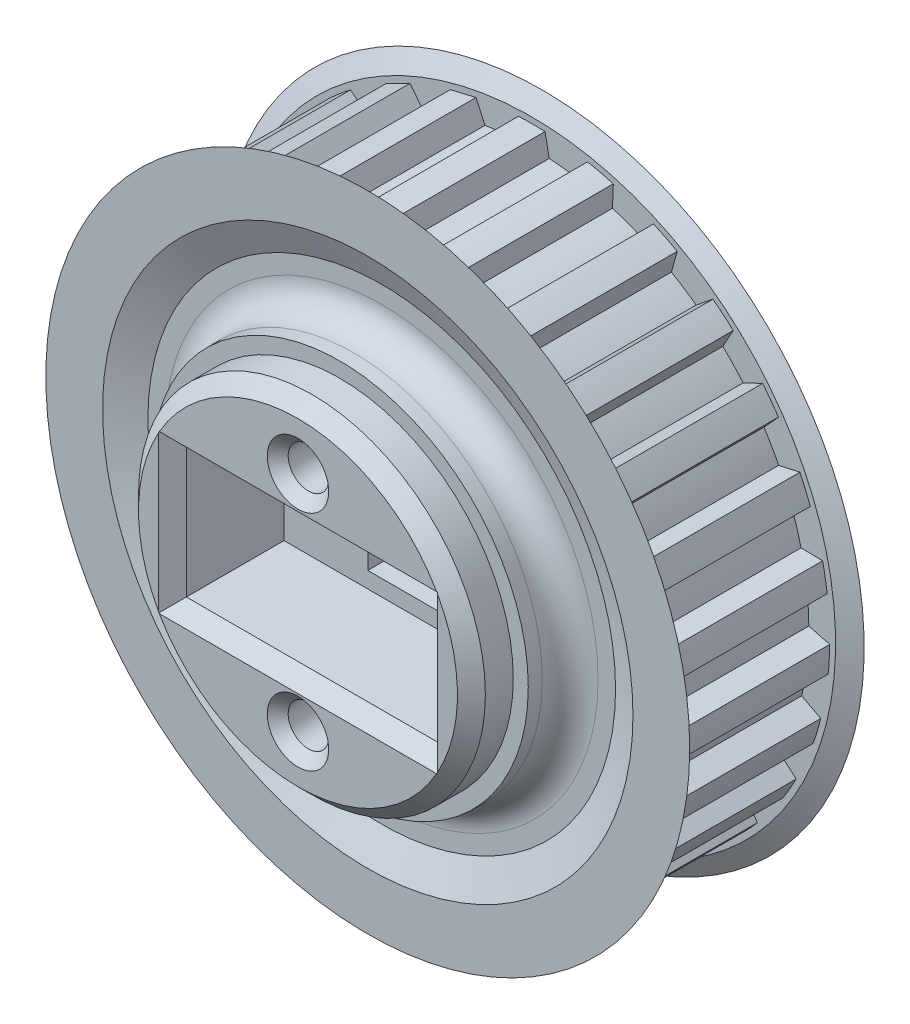
SolidWorks part; units mm, degrees
other "Markup1"
sketch "Sketch8" plane through (-22.8072, 22.8072, -5) normal (-0.0228, 0.8013, -0.5978) x (-0.0343, -0.5983, -0.8006)
sketch "Sketch9" plane through (-23.067, 23.067, -5.7421) normal (-0.0228, 0.8013, -0.5978) x (-0.0343, -0.5983, -0.8006)
sketch "Sketch10" plane through (-23.067, 23.067, -5.7421) normal (-0.0228, 0.8013, -0.5978) x (-0.0343, -0.5983, -0.8006)
material "ABS"
ref_plane "Alzado" through (0, 0, 0) normal (0, 0, 1) x (1, 0, 0)
ref_plane "Planta" through (0, 0, 0) normal (0, 1, 0) x (1, 0, 0)
ref_plane "Vista lateral" through (0, 0, 0) normal (1, 0, 0) x (0, 0, -1)
sketch "Croquis1" plane through (0, 0, 0) normal (0, 0, 1) x (1, 0, 0)
  line L0 (0, 0) -> (0, 14.5885) construction
  line L1 (-0.95, 21.3289) -> (-1.25, 19.8106)
  line L2 (0.95, 21.3289) -> (1.25, 19.8106)
  line L3 (5.8432, 20.5348) -> (5.7849, 18.9883)
  line L4 (3.9944, 20.973) -> (3.3523, 19.5649)
  line L5 (10.4213, 18.6338) -> (10.008, 17.1424)
  line L6 (8.7234, 19.4865) -> (7.7739, 18.2644)
  line L7 (14.4377, 15.7282) -> (13.6916, 14.3723)
  line L8 (12.9822, 16.9495) -> (11.7765, 15.9793)
  line L9 (17.6757, 11.9747) -> (16.637, 10.8274)
  line L10 (16.5411, 13.4987) -> (15.1441, 12.8327)
  line L11 (19.9608, 7.5756) -> (18.6855, 6.6988)
  line L12 (19.2082, 9.3202) -> (17.6953, 8.9943)
  line L13 (21.1698, 2.7681) -> (19.7267, 2.2091)
  line L14 (20.8399, 4.6393) -> (19.2926, 4.6711)
  line L15 (21.2375, -2.1886) -> (19.7044, -2.3998)
  line L16 (21.348, -0.2918) -> (19.8498, 0.096)
  line L17 (20.1604, -7.0273) -> (18.6198, -6.8792)
  line L18 (20.7053, -5.2071) -> (19.3369, -4.4843)
  line L19 (17.9963, -11.4872) -> (16.5315, -10.9878)
  line L20 (18.9463, -9.8417) -> (17.7815, -8.8228)
  line L21 (14.8621, -15.3278) -> (13.5519, -14.5041)
  line L22 (16.166, -13.9457) -> (15.2675, -12.6856)
  line L23 (10.9267, -18.342) -> (9.8417, -17.2384)
  line L24 (12.5141, -17.298) -> (11.9305, -15.8646)
  line L25 (6.4022, -20.3675) -> (5.601, -19.0434)
  line L26 (8.1876, -19.7176) -> (7.9502, -18.1884)
  line L27 (1.5326, -21.2949) -> (1.0583, -19.8218)
  line L28 (3.4197, -21.0743) -> (3.5414, -19.5315)
  line L29 (-3.4197, -21.0743) -> (-3.5414, -19.5315)
  line L30 (-1.5326, -21.2949) -> (-1.0583, -19.8218)
  line L31 (-8.1876, -19.7176) -> (-7.9502, -18.1884)
  line L32 (-6.4022, -20.3675) -> (-5.601, -19.0434)
  line L33 (-12.5141, -17.298) -> (-11.9305, -15.8646)
  line L34 (-10.9267, -18.342) -> (-9.8417, -17.2384)
  line L35 (-16.166, -13.9457) -> (-15.2675, -12.6856)
  line L36 (-14.8621, -15.3278) -> (-13.5519, -14.5041)
  line L37 (-18.9463, -9.8417) -> (-17.7815, -8.8228)
  line L38 (-17.9963, -11.4872) -> (-16.5315, -10.9878)
  line L39 (-20.7053, -5.2071) -> (-19.3369, -4.4843)
  line L40 (-20.1604, -7.0273) -> (-18.6198, -6.8792)
  line L41 (-21.348, -0.2918) -> (-19.8498, 0.096)
  line L42 (-21.2375, -2.1886) -> (-19.7044, -2.3998)
  line L43 (-20.8399, 4.6393) -> (-19.2926, 4.6711)
  line L44 (-21.1698, 2.7681) -> (-19.7267, 2.2091)
  line L45 (-19.2082, 9.3202) -> (-17.6953, 8.9943)
  line L46 (-19.9608, 7.5756) -> (-18.6855, 6.6988)
  line L47 (-16.5411, 13.4987) -> (-15.1441, 12.8327)
  line L48 (-17.6757, 11.9747) -> (-16.637, 10.8274)
  line L49 (-12.9822, 16.9495) -> (-11.7765, 15.9793)
  line L50 (-14.4377, 15.7282) -> (-13.6916, 14.3723)
  line L51 (-8.7234, 19.4865) -> (-7.7739, 18.2644)
  line L52 (-10.4213, 18.6338) -> (-10.008, 17.1424)
  line L53 (-10.4213, 18.6338) -> (-8.7234, 19.4865)
  line L54 (-3.9944, 20.973) -> (-3.3523, 19.5649)
  line L55 (-5.8432, 20.5348) -> (-5.7849, 18.9883)
  line L56 (-5.8432, 20.5348) -> (-3.9944, 20.973)
  arc A0 (-10.008, 17.1424) -> (-11.7765, 15.9793) centre (0, 0) ccw
  arc A1 (3.3523, 19.5649) -> (1.25, 19.8106) centre (0, 0) ccw
  arc A2 (-5.7849, 18.9883) -> (-7.7739, 18.2644) centre (0, 0) ccw
  arc A9 (-12.9822, 16.9495) -> (-14.4377, 15.7282) centre (0, 0) ccw
  arc A10 (-16.5411, 13.4987) -> (-17.6757, 11.9747) centre (0, 0) ccw
  arc A11 (5.8432, 20.5348) -> (3.9944, 20.973) centre (0, 0) ccw
  arc A12 (0.95, 21.3289) -> (-0.95, 21.3289) centre (0, 0) ccw
  arc A16 (10.4213, 18.6338) -> (8.7234, 19.4865) centre (0, 0) ccw
  arc A17 (14.4377, 15.7282) -> (12.9822, 16.9495) centre (0, 0) ccw
  arc A18 (17.6757, 11.9747) -> (16.5411, 13.4987) centre (0, 0) ccw
  arc A19 (19.9608, 7.5756) -> (19.2082, 9.3202) centre (0, 0) ccw
  arc A20 (21.1698, 2.7681) -> (20.8399, 4.6393) centre (0, 0) ccw
  arc A21 (21.2375, -2.1886) -> (21.348, -0.2918) centre (0, 0) ccw
  arc A22 (20.1604, -7.0273) -> (20.7053, -5.2071) centre (0, 0) ccw
  arc A23 (17.9963, -11.4872) -> (18.9463, -9.8417) centre (0, 0) ccw
  arc A24 (14.8621, -15.3278) -> (16.166, -13.9457) centre (0, 0) ccw
  arc A25 (10.9267, -18.342) -> (12.5141, -17.298) centre (0, 0) ccw
  arc A26 (-8.1876, -19.7176) -> (-6.4022, -20.3675) centre (0, 0) ccw
  arc A27 (-12.5141, -17.298) -> (-10.9267, -18.342) centre (0, 0) ccw
  arc A28 (-16.166, -13.9457) -> (-14.8621, -15.3278) centre (0, 0) ccw
  arc A29 (-20.7053, -5.2071) -> (-20.1604, -7.0273) centre (0, 0) ccw
  arc A30 (-21.348, -0.2918) -> (-21.2375, -2.1886) centre (0, 0) ccw
  arc A31 (-20.8399, 4.6393) -> (-21.1698, 2.7681) centre (0, 0) ccw
  arc A32 (-19.2082, 9.3202) -> (-19.9608, 7.5756) centre (0, 0) ccw
  arc A33 (-3.4197, -21.0743) -> (-1.5326, -21.2949) centre (0, 0) ccw
  arc A34 (1.5326, -21.2949) -> (3.4197, -21.0743) centre (0, 0) ccw
  arc A35 (6.4022, -20.3675) -> (8.1876, -19.7176) centre (0, 0) ccw
  arc A36 (7.7739, 18.2644) -> (5.7849, 18.9883) centre (0, 0) ccw
  arc A37 (11.7765, 15.9793) -> (10.008, 17.1424) centre (0, 0) ccw
  arc A39 (-1.25, 19.8106) -> (-3.3523, 19.5649) centre (0, 0) ccw
  arc A43 (15.1441, 12.8327) -> (13.6916, 14.3723) centre (0, 0) ccw
  arc A44 (17.6953, 8.9943) -> (16.637, 10.8274) centre (0, 0) ccw
  arc A45 (19.2926, 4.6711) -> (18.6855, 6.6988) centre (0, 0) ccw
  arc A46 (19.8498, 0.096) -> (19.7267, 2.2091) centre (0, 0) ccw
  arc A47 (19.3369, -4.4843) -> (19.7044, -2.3998) centre (0, 0) ccw
  arc A48 (17.7815, -8.8228) -> (18.6198, -6.8792) centre (0, 0) ccw
  arc A49 (15.2675, -12.6856) -> (16.5315, -10.9878) centre (0, 0) ccw
  arc A50 (11.9305, -15.8646) -> (13.5519, -14.5041) centre (0, 0) ccw
  arc A51 (7.9502, -18.1884) -> (9.8417, -17.2384) centre (0, 0) ccw
  arc A52 (3.5414, -19.5315) -> (5.601, -19.0434) centre (0, 0) ccw
  arc A53 (-1.0583, -19.8218) -> (1.0583, -19.8218) centre (0, 0) ccw
  arc A54 (-5.601, -19.0434) -> (-3.5414, -19.5315) centre (0, 0) ccw
  arc A55 (-9.8417, -17.2384) -> (-7.9502, -18.1884) centre (0, 0) ccw
  arc A56 (-13.5519, -14.5041) -> (-11.9305, -15.8646) centre (0, 0) ccw
  arc A57 (-16.5315, -10.9878) -> (-15.2675, -12.6856) centre (0, 0) ccw
  arc A58 (-18.6198, -6.8792) -> (-17.7815, -8.8228) centre (0, 0) ccw
  arc A59 (-19.7044, -2.3998) -> (-19.3369, -4.4843) centre (0, 0) ccw
  arc A60 (-19.7267, 2.2091) -> (-19.8498, 0.096) centre (0, 0) ccw
  arc A61 (-18.6855, 6.6988) -> (-19.2926, 4.6711) centre (0, 0) ccw
  arc A62 (-16.637, 10.8274) -> (-17.6953, 8.9943) centre (0, 0) ccw
  arc A63 (-13.6916, 14.3723) -> (-15.1441, 12.8327) centre (0, 0) ccw
  arc A71 (-18.9463, -9.8417) -> (-17.9963, -11.4872) centre (0, 0) ccw
  circle A72 centre (0, 0) radius 1.5
  point P151 (0, 0)
  dimension "D1" = 21.35
  dimension "D6" = 3
  dimension "D5" = 1.5
  dimension "D2" = 2.5
  dimension "D3" = 1.9
  dimension "D4" = 27
extrude "Saliente-Extruir1" add sketch "Croquis1" along normal blind 11
sketch "Croquis2" plane through (0, 0, 11) normal (0, 0, 1) x (1, 0, 0)
  circle A0 centre (0, 0) radius 23.5
  circle A1 centre (0, 0) radius 1.5
  circle A2 centre (0, 0) radius 1.5 construction
  dimension "D1" = 47
extrude "Saliente-Extruir2" add sketch "Croquis2" along normal blind 0.75
sketch "Croquis3" plane through (0, 0, 11.75) normal (0, 0, 1) x (1, 0, 0)
  circle A0 centre (0, 0) radius 1.5
  circle A1 centre (0, 0) radius 12.425
  circle A3 centre (0, 0) radius 1.5 construction
  dimension "D1" = 24.85
sketch "Croquis4" plane through (0, 0, 0) normal (0, 0, -1) x (-1, 0, 0)
  circle A0 centre (0, 0) radius 1.5
  circle A1 centre (0, 0) radius 12.35
  circle A2 centre (0, 0) radius 1.5 construction
  dimension "D1" = 24.7
extrude "Saliente-Extruir4" add sketch "Croquis4" along normal blind 5.5
sketch "Croquis6" plane through (0, 0, 0) normal (0, 0, -1) x (-1, 0, 0)
  circle A0 centre (0, 0) radius 23.5
  circle A1 centre (0, 0) radius 1.5
  circle A2 centre (0, 0) radius 1.5 construction
  dimension "D1" = 47
extrude "Saliente-Extruir6" add sketch "Croquis6" along normal blind 0.75
sketch "Sketch6" plane through (0, 0, -0.75) normal (0, 0, -1) x (-1, 0, 0)
  circle A0 centre (0, 0) radius 12.35
  circle A1 centre (0, 0) radius 18.5
  circle A2 centre (0, 0) radius 12.35 construction
  dimension "D1" = 37
extrude "Cut-Extrude3" cut sketch "Sketch6" against normal blind 1
sketch "Croquis5" plane through (0, 0, 0.25) normal (0, 0, -1) x (-1, 0, 0)
  circle A0 centre (0, 0) radius 1.5
  circle A1 centre (0, 0) radius 13.5
  circle A2 centre (0, 0) radius 1.5 construction
  dimension "D1" = 27
extrude "Saliente-Extruir5" add sketch "Croquis5" along normal blind 2.75
chamfer "Chaflán2" distance 1 angle 60 2 edges at (-23.5, 0, 0) (23.5, 0, 11)
extrude "Saliente-Extruir7" add sketch "Croquis3" along normal blind 5
sketch "Sketch7" plane through (0, 0, 11.75) normal (0, 0, 1) x (1, 0, 0)
  circle A0 centre (0, 0) radius 12.425
  circle A1 centre (0, 0) radius 19
  circle A2 centre (0, 0) radius 12.425 construction
  dimension "D1" = 38
extrude "Cut-Extrude4" cut sketch "Sketch7" against normal blind 1
chamfer "Chaflán4" distance 1 angle 45 1 edges at (12.425, 0, 16.75)
sketch "Croquis7" plane through (0, 0, 10.75) normal (0, 0, 1) x (1, 0, 0)
  circle A0 centre (0, 0) radius 1.5
  circle A1 centre (0, 0) radius 13.5
  circle A2 centre (0, 0) radius 1.5 construction
  dimension "D1" = 27
extrude "Saliente-Extruir8" add sketch "Croquis7" along normal blind 3
sketch "Croquis8" plane through (0, 0, 0) normal (0, 0, 1) x (1, 0, 0)
  line L0 (0, 0) -> (6.706, 0) construction
  line L1 (-3, 3.5) -> (3, 3.5)
  line L2 (-3, 3.5) -> (-3, -3.5)
  line L3 (-3, -3.5) -> (3, -3.5)
  line L4 (3, 3.5) -> (3, -3.5)
  line L5 (-3, 3.5) -> (3, -3.5) construction
  line L6 (-3, -3.5) -> (3, 3.5) construction
  circle A0 centre (0, 8) radius 1.45
  circle A1 centre (0, -8) radius 1.45
  point P0 (0, 0)
  dimension "D1" = 2.9
  dimension "D2" = 7
  dimension "D3" = 6
  dimension "D4" = 16
extrude "Cortar-Extruir1" cut sketch "Croquis8" against normal through all both and the other way through all
sketch "Croquis10" plane through (0, 0, 16.75) normal (0, 0, 1) x (1, 0, 0)
  line L1 (9, 4.65) -> (-9, 4.65)
  line L2 (9, 4.65) -> (9, -4.65)
  line L3 (9, -4.65) -> (-9, -4.65)
  line L4 (-9, 4.65) -> (-9, -4.65)
  line L5 (9, 4.65) -> (-9, -4.65) construction
  line L6 (9, -4.65) -> (-9, 4.65) construction
  point P0 (0, 0)
  dimension "D1" = 9.3
  dimension "D2" = 18
extrude "Cortar-Extruir3" cut sketch "Croquis10" against normal blind 8
chamfer "Chaflán5" distance 1 angle 45 8 edges at (-3, 0, -5.5) (0, 3.5, -5.5) (3, 0, -5.5) (0, -3.5, -5.5) (9, 0, 16.75) (0, 4.65, 16.75) (-9, 0, 16.75) (0, -4.65, 16.75)
sketch "Sketch1" plane through (0, 0, -5.5) normal (0, 0, -1) x (-1, 0, 0)
  circle A0 centre (0, 0) radius 12.35
  circle A1 centre (0, 0) radius 12.35 construction
  circle A2 centre (0, 8) radius 1.45
  circle A3 centre (0, -8) radius 1.45
  circle A4 centre (0, 8) radius 1.45 construction
extrude "Boss-Extrude1" add sketch "Sketch1" against normal blind 5
sketch "Sketch2" plane through (0, 0, -5.5) normal (0, 0, -1) x (-1, 0, 0)
  line L0 (0, 17.274) -> (0, -20.0751) construction
  line L1 (-6.5, 0) -> (6.5, 0) construction
  circle A0 centre (-6.5, 0) radius 1.45
  circle A1 centre (6.5, 0) radius 1.45
  dimension "D1" = 2.9
  dimension "D2" = 13
extrude "Cut-Extrude1" cut sketch "Sketch2" against normal through all
sketch "Sketch4" plane through (0, 0, 16.75) normal (0, 0, 1) x (1, 0, 0)
  line L0 (-3, -3.5) -> (3, -3.5) construction
  line L1 (3, 3.5) -> (-3, 3.5)
  line L2 (3, 3.5) -> (3, -3.5)
  line L3 (3, -3.5) -> (-3, -3.5)
  line L4 (-3, 3.5) -> (-3, -3.5)
  line L5 (3, 3.5) -> (-3, -3.5) construction
  line L6 (3, -3.5) -> (-3, 3.5) construction
  point P0 (0, 0)
  dimension "D1" = 6
extrude "Cut-Extrude2" cut sketch "Sketch4" against normal blind 30
chamfer "Chamfer3" distance 1.25 angle 45 4 edges at (-3, 0, -5.5) (0, 3.5, -5.5) (3, 0, -5.5) (0, -3.5, -5.5)
chamfer "Chamfer2" distance 0.75 angle 45 1 edges at (-12.35, 0, -5.5)
chamfer "Chamfer4" distance 1 angle 66 2 edges at (19, 0, 10.75) (-18.5, 0, 0.25)
chamfer "Chamfer5" distance 0.75 angle 45 4 edges at (-7.95, 0, 8.75) (1.45, 8, 16.75) (5.05, 0, 8.75) (1.45, -8, 16.75)
fillet "Fillet1" radius 2 2 edges at (-13.5, 0, 0.25) (13.5, 0, 10.75)
chamfer "Chamfer6" distance 1.2 angle 45 4 edges at (1.45, 8, -5.5) (5.05, 0, -5.5) (1.45, -8, -5.5) (-5.05, 0, -5.5)
